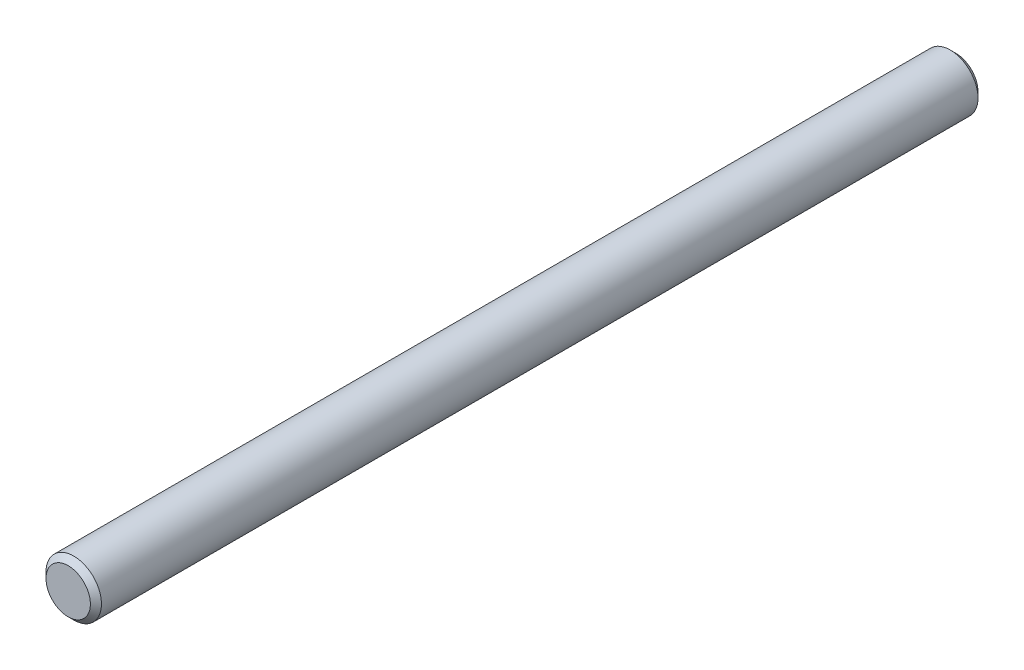
SolidWorks part; units mm, degrees
ref_plane "Front" through (0, 0, 0) normal (0, 0, 1) x (1, 0, 0)
ref_plane "Top" through (0, 0, 0) normal (0, 1, 0) x (1, 0, 0)
ref_plane "Right" through (0, 0, 0) normal (1, 0, 0) x (0, 0, -1)
sketch "Sketch1" plane through (0, 0, 0) normal (0, 0, 1) x (1, 0, 0)
  circle A0 centre (0, 0) radius 9.525
  dimension "dia" = 19.05
extrude "Extrude1" add sketch "Sketch1" along normal mid plane 304.8
sketch "Sketch2" plane through (0, 0, 0) normal (1, 0, 0) x (0, 0, -1)
  line L0 (152.4, 9.525) -> (149.9, 9.525) construction
  line L1 (152.4, 9.525) -> (-152.4, 9.525) construction
  line L2 (149.9, 9.525) -> (111.8, 9.525) construction
  line L3 (111.8, 9.525) -> (109.8, 9.525) construction
  line L4 (109.8, 9.525) -> (99.8, 9.525) construction
  line L5 (99.8, 9.525) -> (97.9, 9.525) construction
  line L6 (111.8, 9.525) -> (111.8, -9.4601) construction
  line L7 (99.8, 9.525) -> (-65.2, 9.525) construction
  line L8 (-65.2, 9.525) -> (-67.2, 9.525) construction
  line L9 (-67.2, 9.525) -> (-67.2, -9.525) construction
  line L10 (-152.4, -9.525) -> (152.4, -9.525) construction
  point P0 (-152.4, 9.525)
  point P1 (152.4, 9.525)
  dimension "D1" = 2.5
  dimension "D2" = 38.1
  dimension "D3" = 2
  dimension "D4" = 10
  dimension "D5" = 1.9
  dimension "D6" = 165
  dimension "D7" = 2
chamfer "Chamfer1" distance 1.905 angle 45 2 edges at (9.525, 0, -152.4) (9.525, 0, 152.4)
equation "\"D1@Chamfer1\" = \"dia@Sketch1\" * .1"
